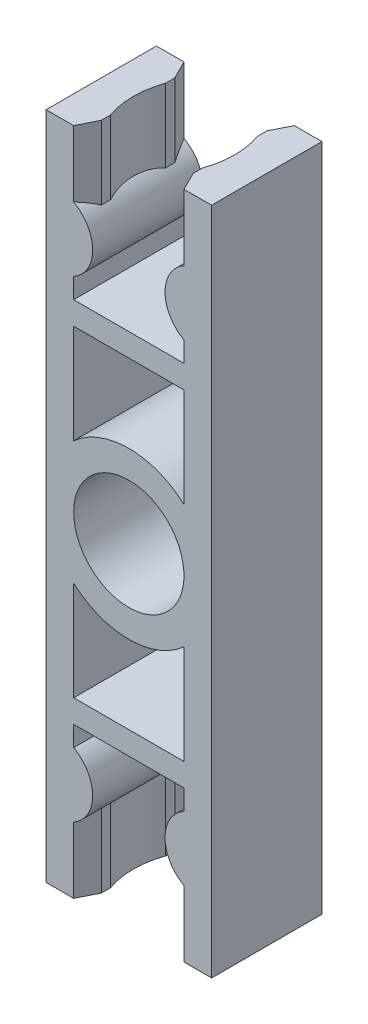
SolidWorks part; units mm, degrees
ref_plane "前视基准面" through (0, 0, 0) normal (0, 0, 1) x (1, 0, 0)
ref_plane "上视基准面" through (0, 0, 0) normal (0, 1, 0) x (1, 0, 0)
ref_plane "右视基准面" through (0, 0, 0) normal (1, 0, 0) x (0, 0, -1)
sketch "草图1" plane through (0, 0, 0) normal (0, 0, 1) x (1, 0, 0)
  line L0 (-4.5, 0) -> (-4.5, -18.2)
  line L1 (4.5, 0) -> (4.5, -18.2)
  line L2 (-4.5, -18.2) -> (-3, -18.2)
  line L3 (-3, -18.2) -> (-3, -14.6)
  line L4 (4.5, -18.2) -> (3, -18.2)
  line L5 (3, -18.2) -> (3, -14.6)
  line L6 (-3, -11.1) -> (-3, -10)
  line L7 (-3, -10) -> (3, -10)
  line L8 (3, -10) -> (3, -11.1)
  arc A0 (4.5, 0) -> (-4.5, 0) centre (0, 0) ccw
  arc A1 (-3, -11.1) -> (-3, -14.6) centre (-3.9682, -12.85) cw
  arc A2 (3, -11.1) -> (3, -14.6) centre (3.9682, -12.85) ccw
  point P1 (0, 4.5)
  dimension "D1" = 9
  dimension "D10" = 14.5
  dimension "D11" = 2
  dimension "D12" = 2
  dimension "D2" = 18.2
  dimension "D3" = 18.2
  dimension "D4" = 1.5
  dimension "D5" = 1.5
  dimension "D6" = 1.1
  dimension "D7" = 1.1
  dimension "D8" = 3.5
  dimension "D9" = 3.5
extrude "凸台-拉伸1" add sketch "草图1" along normal blind 6
sketch "草图2" plane through (0, 0, 0) normal (0, 0, 1) x (1, 0, 0)
  line L0 (-3, -8.75) -> (-3, -3.3541)
  line L1 (3, -8.75) -> (3, -3.3541)
  line L2 (-3, -8.75) -> (3, -8.75)
  line L3 (-3, -10) -> (3, -10) construction
  circle A0 centre (0, 0) radius 3
  arc A1 (-3, -3.3541) -> (3, -3.3541) centre (0, 0) ccw
  dimension "D1" = 6
  dimension "D2" = 9
  dimension "D3" = 1.25
extrude "切除-拉伸1" cut sketch "草图2" along normal through all
sketch "草图3" plane through (0, -18.2, 0) normal (0, -1, 0) x (1, 0, 0)
  line L0 (-3, 6) -> (-3, 0)
  line L1 (-3, 0) -> (-2.5, 1)
  line L2 (-2.5, 1) -> (-2.5, 1.5)
  line L3 (-3, 6) -> (-2.5, 5)
  line L4 (-2.5, 5) -> (-2.5, 4.5)
  line L5 (0, 0) -> (0, 6.4845) construction
  line L6 (3, 0) -> (2.5, 1)
  line L7 (2.5, 1) -> (2.5, 1.5)
  line L8 (2.5, 5) -> (2.5, 4.5)
  line L9 (3, 6) -> (2.5, 5)
  line L10 (3, 6) -> (3, 0)
  arc A0 (-2.5, 1.5) -> (-2.5, 4.5) centre (1.7426, 3) cw
  arc A1 (2.5, 1.5) -> (2.5, 4.5) centre (-1.7426, 3) ccw
  dimension "D7" = 4.5
  dimension "D1" = 0.5
  dimension "D2" = 0.5
  dimension "D3" = 0.5
  dimension "D4" = 0.5
  dimension "D5" = 1.5
  dimension "D6" = 1.5
extrude "凸台-拉伸2" add sketch "草图3" against normal up to next
ref_axis "Axis" through (0, 0, 0) along (0, 0, 1)
pattern_circular "阵列(圆周)1" count 2 every 180 about axis through (0, 0, 0) along (0, 0, 1) of "凸台-拉伸1", "切除-拉伸1", "凸台-拉伸2"
